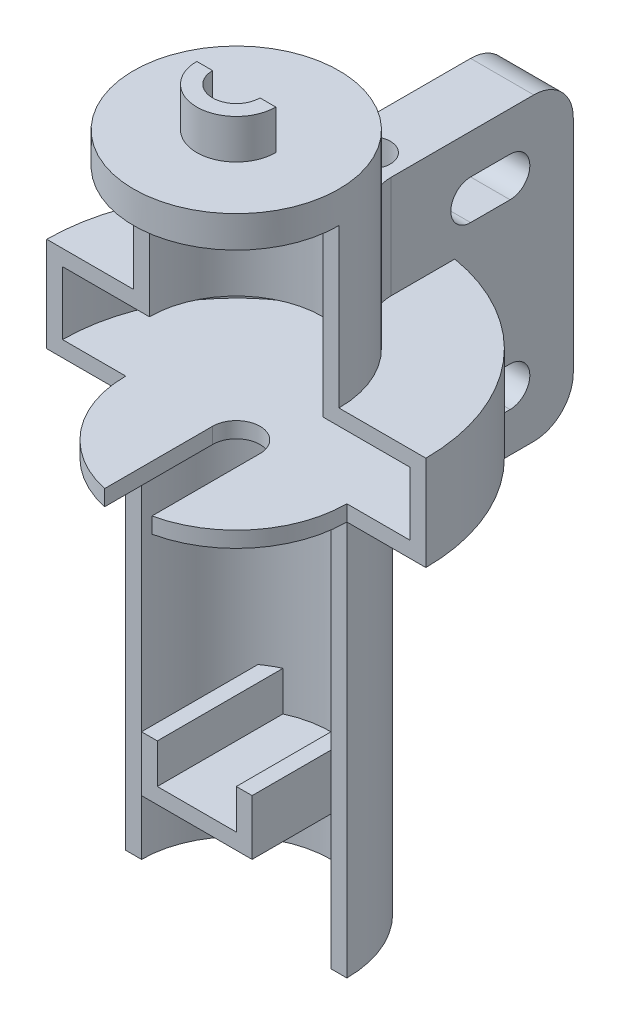
SolidWorks part; units mm, degrees
ref_plane "Front Plane" through (0, 0, 0) normal (0, 0, 1) x (1, 0, 0)
ref_plane "Top Plane" through (0, 0, 0) normal (0, 1, 0) x (1, 0, 0)
ref_plane "Right Plane" through (0, 0, 0) normal (1, 0, 0) x (0, 0, -1)
sketch "Sketch1" plane through (0, 0, 0) normal (0, 1, 0) x (1, 0, 0)
  line L0 (3, 0) -> (3, -13.6748)
  line L1 (-3, 0) -> (-3, -13.6748)
  line L2 (-14, 0) -> (-24, 0)
  line L3 (14, 0) -> (24, 0)
  circle A0 centre (0, 0) radius 14
  circle A1 centre (0, 0) radius 3
  arc A2 (24, 0) -> (-24, 0) centre (0, 0) ccw
  arc A3 (14, 0) -> (-14, 0) centre (0, 0) ccw
  dimension "D1" = 28
  dimension "D2" = 6
  dimension "D3" = 10
extrude "Motor-frontplate" add sketch "Sketch1" along normal blind 2 contours A1 L0 A0 L1 | L3 A2 L2 A3 region at (0, 0, -3.3937)
sketch "Sketch2" plane through (0, 0, 0) normal (0, -1, 0) x (1, 0, 0)
  line L2 (-12, 0) -> (-14, 0)
  line L3 (12, 0) -> (14, 0)
  arc A1 (-14, 0) -> (14, 0) centre (0, 0) ccw
  arc A3 (14, 0) -> (3, 13.6748) centre (0, 0) ccw construction
  arc A4 (-12, 0) -> (12, 0) centre (0, 0) ccw
  dimension "D1" = 2
extrude "Motorkrybbe" add sketch "Sketch2" along normal blind 50 contours A4 L3 A1 L2
sketch "Sketch5" plane through (0, 2, 0) normal (0, 1, 0) x (1, 0, 0)
  line L0 (-24, 0) -> (-22, 0)
  line L1 (24, 0) -> (22, 0)
  arc A1 (24, 0) -> (-24, 0) centre (0, 0) ccw construction
  arc A2 (22, 0) -> (-22, 0) centre (0, 0) ccw
  arc A3 (22, 0) -> (-22, 0) centre (0, 0) ccw
  arc A4 (24, 0) -> (-24, 0) centre (0, 0) ccw
  dimension "D1" = 2
extrude "Skygge - Kappe" add sketch "Sketch5" along normal blind 8 contours A3 L0 A4 L1
sketch "Sketch6" plane through (0, 10, 0) normal (0, 1, 0) x (1, 0, 0)
  line L0 (-24, 0) -> (-11, 0)
  line L1 (11, 0) -> (24, 0)
  arc A0 (-11, 0) -> (11, 0) centre (0, 0) cw
  arc A1 (24, 0) -> (-24, 0) centre (0, 0) ccw construction
  arc A2 (24, 0) -> (-24, 0) centre (0, 0) ccw
  dimension "D1" = 11
extrude "Skygge - Topp" add sketch "Sketch6" along normal blind 2
sketch "Sketch7" plane through (0, 12, 0) normal (0, 1, 0) x (1, 0, 0)
  line L0 (-4, 12.3693) -> (-4, 23.6643)
  line L1 (4, 23.6643) -> (4, 12.3693)
  arc A0 (24, 0) -> (-24, 0) centre (0, 0) ccw construction
  arc A1 (11, 0) -> (-11, 0) centre (0, 0) ccw construction
  arc A2 (24, 0) -> (-24, 0) centre (0, 0) ccw
  arc A3 (11, 0) -> (-11, 0) centre (0, 0) ccw
  arc A4 (4, 12.3693) -> (-4, 12.3693) centre (0, 0) ccw
  arc A5 (4, 23.6643) -> (-4, 23.6643) centre (0, 0) ccw
  dimension "D3" = 2
  dimension "D1" = 4
  dimension "D2" = 4
extrude "LEDholder - Topp" add sketch "Sketch7" along normal blind 13 contours L1 A4 L0 A5
sketch "Sketch8" plane through (0, 0, 0) normal (0, -1, 0) x (1, 0, 0)
  line L0 (4, -23.6643) -> (4, -13.4164)
  line L1 (4, -23.6643) -> (4, -12.3693) construction
  line L2 (-4, -23.6643) -> (-4, -13.4164)
  line L3 (-4, -12.3693) -> (-4, -23.6643) construction
  arc A0 (-14, 0) -> (14, 0) centre (0, 0) ccw construction
  arc A1 (4, -13.4164) -> (-4.105, -13.3846) centre (0, 0) cw
  arc A2 (4, -23.6643) -> (-4, -23.6643) centre (0, 0) cw
  arc M1 (14, 0) -> (-14, 0) centre (0, 0) cw
  arc M3 (-24, 0) -> (24, 0) centre (0, 0) ccw
extrude "LEDholder - Bunn" add sketch "Sketch8" along normal blind 13 contours L2 L0 M3 M1 region at (0, 0, -18.8468)
sketch "Sketch10" plane through (0, -13, 0) normal (0, -1, 0) x (1, 0, 0)
  line L2 (0, 0) -> (0, -14)
  line L3 (0, -14) -> (0, -14.5)
  line L4 (0, -14.5) -> (0, -17)
  arc A0 (-4, -13.4164) -> (4, -13.4164) centre (0, 0) ccw construction
  arc A1 (-4, -13.4164) -> (4, -13.4164) centre (0, 0) ccw
  circle A3 centre (0, -17) radius 2.5
  dimension "D1" = 5
  dimension "D2" = 0.5
extrude "LEDhull" cut sketch "Sketch10" against normal through all contours A3 region at (-1.7178, -13, -18.7178)
sketch "Sketch11" plane through (0, 12, 0) normal (0, 1, 0) x (1, 0, 0)
  line L0 (-24, 0) -> (-11, 0) construction
  line L1 (11, 0) -> (24, 0) construction
  line L2 (-13, 0) -> (-11, 0)
  line L3 (13, 0) -> (11, 0)
  arc A0 (-11, 0) -> (11, 0) centre (0, 0) cw
  arc A1 (11, 0) -> (-11, 0) centre (0, 0) ccw construction
  arc A2 (-13, 0) -> (13, 0) centre (0, 0) cw
  dimension "D1" = 2
extrude "Rotorkappe - Vegg" add sketch "Sketch11" along normal blind 20
sketch "Sketch12" plane through (0, 32, 0) normal (0, 1, 0) x (1, 0, 0)
  circle A0 centre (0, 0) radius 13
extrude "Laserholder" add sketch "Sketch12" along normal blind 4
hole_wizard "Laser - hull" positions "Sketch13" profile "Sketch15" hole size "Ø6.0" standard "ISO" end condition up to next
sketch "Sketch13" plane through (0, 36, 0) normal (0, 1, 0) x (1, 0, 0)
  point P0 (0, 0)
sketch "Sketch15" plane through (0, 36, 0) normal (1, 0, 0) x (0, 0, 1)
  line L0 (0, 0) -> (0, 4)
  line L1 (0, 4) -> (3, 4)
  line L2 (3, 4) -> (3, 0)
  line L5 (3, 0) -> (0, 0)
  line L11 (0, -6.35) -> (0, 107.95) construction
  dimension "Thru Hole Dia." = 6
  dimension "Thru Hole Depth" = 4
sketch "Sketch19" plane through (0, 0, 0) normal (0, 0, 1) x (1, 0, 0)
  line L0 (0, -36) -> (-5, -36)
  line L9 (-5, -36) -> (-5, -31)
  line L10 (-5, -31) -> (-7, -31)
  line L11 (-7, -31) -> (-7, -38)
  line L12 (-7, -38) -> (0, -38)
  line L13 (0, -38) -> (0, -36)
  line L14 (0, 0) -> (0, -36) construction
  dimension "D1" = 31
  dimension "D2" = 2
  dimension "D3" = 5
  dimension "D4" = 2
  dimension "D5" = 5
extrude "Boss-Extrude12" add sketch "Sketch19" along normal blind 5 and the other way up to next
mirror "Mirror2" about plane through (0, -38, -24.002) normal (1, 0, 0) of "Boss-Extrude12"
sketch "Sketch20" plane through (0, 25, 0) normal (0, 1, 0) x (1, 0, 0)
  line L0 (4, 23.6643) -> (4, 38.6643)
  line L1 (4, 38.6643) -> (-4, 38.6643)
  line L2 (-4, 38.6643) -> (-4, 23.6643)
  arc A0 (4, 23.6643) -> (-4, 23.6643) centre (0, 0) ccw construction
  arc A1 (4, 23.6643) -> (-4, 23.6643) centre (0, 0) ccw
  dimension "D1" = 15
extrude "LED - kabelholder" add sketch "Sketch20" against normal blind 38
sketch "Sketch21" plane through (4, 0, 0) normal (1, 0, 0) x (0, 0, -1)
  line L0 (25.6643, 17.5) -> (30.6643, 17.5) construction
  line L1 (25.6643, 20) -> (30.6643, 20)
  line L2 (25.6643, 15) -> (30.6643, 15)
  line L3 (38.6643, -13) -> (38.6643, 25) construction
  line L4 (12.3693, 25) -> (38.6643, -13) construction
  line L5 (38.6643, 25) -> (12.3693, 25) construction
  line L6 (25.5168, 6) -> (38.6643, 6)
  line L7 (25.6643, -5.5) -> (30.6643, -5.5) construction
  line L8 (25.6643, -8) -> (30.6643, -8)
  line L9 (25.6643, -3) -> (30.6643, -3)
  arc A0 (25.6643, 20) -> (25.6643, 15) centre (25.6643, 17.5) ccw
  arc A1 (30.6643, 15) -> (30.6643, 20) centre (30.6643, 17.5) ccw
  arc A2 (25.6643, -8) -> (25.6643, -3) centre (25.6643, -5.5) cw
  arc A3 (30.6643, -3) -> (30.6643, -8) centre (30.6643, -5.5) cw
  point P2 (28.1643, 17.5)
  point P19 (28.1643, -5.5)
  dimension "D1" = 8
  dimension "D2" = 5
  dimension "D3" = 5
  dimension "D4" = 5
extrude "Kabelholder - hull" cut sketch "Sketch21" against normal up to next contours L2 A1 L1 A0 | A3 L9 A2 L8 region at (4, 17.5, -28.1643) region at (4, -5.5, -28.1643)
fillet "Fillet1" radius 5 2 edges at (0, -13, -38.6643) (0, 25, -38.6643)
sketch "Sketch22" plane through (0, 36, 0) normal (0, 1, 0) x (1, 0, 0)
  line L0 (-3, 0) -> (-5, 0)
  line L1 (3, 0) -> (5, 0)
  circle A1 centre (0, 0) radius 3 construction
  arc A2 (3, 0) -> (-3, 0) centre (0, 0) cw
  arc A3 (5, 0) -> (-5, 0) centre (0, 0) cw
  dimension "D1" = 2
extrude "Boss-Extrude14" add sketch "Sketch22" along normal blind 5
fillet "Fillet3" radius 5 4 edges at (-4, -6.5, -13.4164) (-4, 18.5, -12.3693) (4, -6.5, -13.4164) (4, 18.5, -12.3693)
